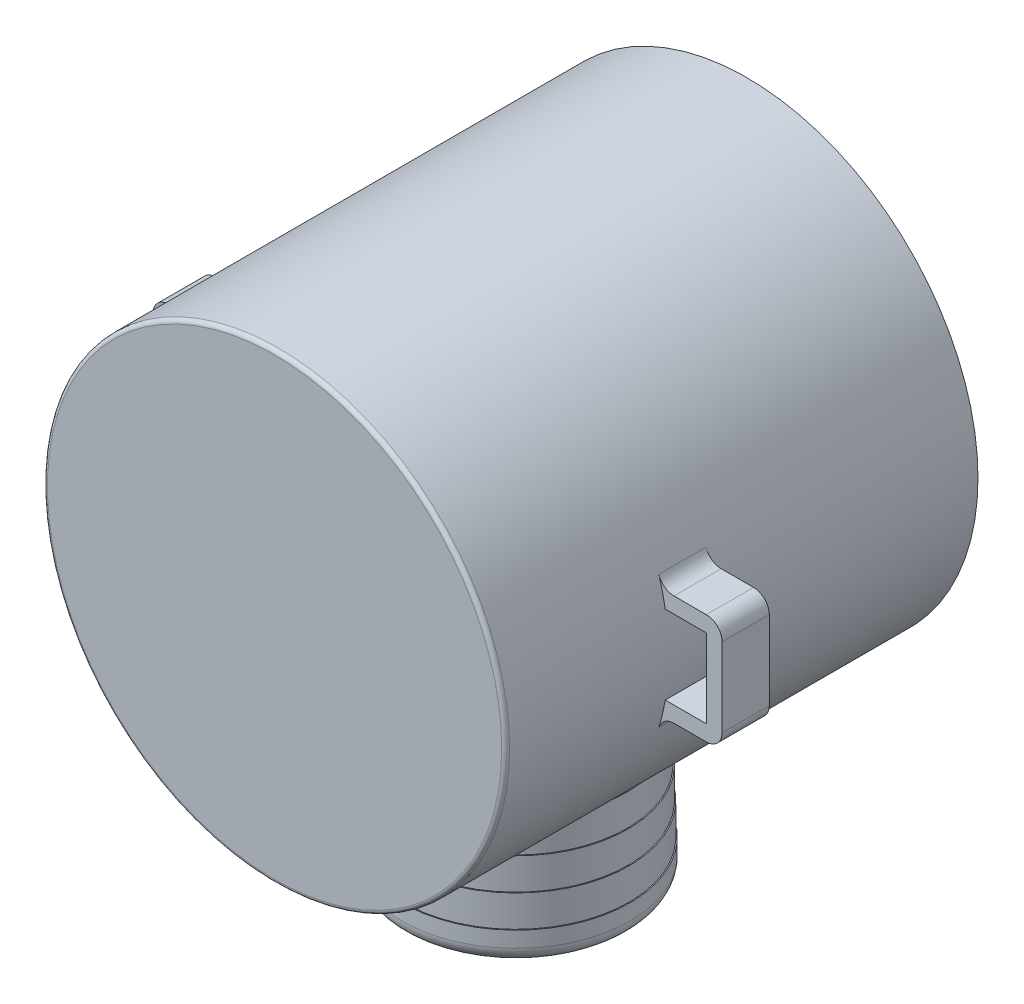
SolidWorks part; units mm, degrees
note: The reader was unsure of these and kept them because the rebuilt part matched: shared geometry of "Sketch3<3>".
ref_plane "Front Plane" through (0, 0, 0) normal (0, 0, 1) x (1, 0, 0)
ref_plane "Top Plane" through (0, 0, 0) normal (0, 1, 0) x (1, 0, 0)
ref_plane "Right Plane" through (0, 0, 0) normal (1, 0, 0) x (0, 0, -1)
sketch "Sketch1" plane through (0, 0, 0) normal (0, 0, 1) x (1, 0, 0)
  circle A0 centre (0, 0) radius 29.35
  circle A1 centre (0, 0) radius 27.5
  dimension "D1" = 55
  dimension "D2" = 58.7
extrude "Boss-Extrude1" add sketch "Sketch1" along normal blind 60
ref_plane "Plane1" through (0, 0, 33.3) normal (0, 0, 1) x (1, 0, 0)
sketch "Sketch2" plane through (0, 0, 33.3) normal (0, 0, 1) x (1, 0, 0)
  line L0 (-48.0014, 0) -> (58.2597, 0) construction
  line L1 (-28.503, 7) -> (-36.143, 7)
  line L2 (-36.143, 7) -> (-36.143, -7)
  line L3 (-36.143, -7) -> (-28.503, -7)
  line L4 (0, 39.654) -> (0, -46.8411) construction
  line L5 (-28.921, 5) -> (-34.143, 5)
  line L6 (-34.143, 5) -> (-34.143, -5)
  line L7 (-34.143, -5) -> (-28.921, -5)
  line L8 (-34.143, -5) -> (-28.503, -5) construction
  line L9 (-28.503, 5) -> (-34.143, 5) construction
  line L10 (28.503, 7) -> (36.143, 7)
  line L11 (36.143, 7) -> (36.143, -7)
  line L12 (36.143, -7) -> (28.503, -7)
  line L13 (34.143, -5) -> (28.921, -5)
  line L14 (34.143, 5) -> (34.143, -5)
  line L15 (28.921, 5) -> (34.143, 5)
  circle A0 centre (0, 0) radius 29.35 construction
  arc A2 (-28.503, 7) -> (-28.921, 5) centre (0, 0) ccw
  arc A3 (-28.921, -5) -> (-28.503, -7) centre (0, 0) ccw
  arc A4 (28.921, -5) -> (28.503, -7) centre (0, 0) cw
  arc A5 (28.503, 7) -> (28.921, 5) centre (0, 0) cw
  point P11 (-36.143, 0)
  dimension "D1" = 14
  dimension "D2" = 7.64
  dimension "D3" = 2
extrude "Boss-Extrude2" add sketch "Sketch2" along normal blind 6
fillet "Fillet1" radius 2 8 edges at (36.143, 7, 36.3) (36.143, -7, 36.3) (-36.143, 7, 36.3) (-36.143, -7, 36.3) (-28.503, -7, 36.3) (-28.503, 7, 36.3) (28.503, -7, 36.3) (28.503, 7, 36.3)
fillet "Fillet2" radius 0.5 1 edges at (29.35, 0, 60)
ref_plane "Plane3" through (0, -29.35, 0) normal (0, -1, 0) x (-1, 0, 0)
sketch "Sketch3" plane through (0, -29.35, 0) normal (0, -1, 0) x (-1, 0, 0)
  line L0 (29.35, -59.5) -> (29.35, 0) construction
  line L1 (-29.35, 0) -> (-29.35, -59.5) construction
  line L2 (-29.35, -59.5) -> (29.35, -59.5) construction
  line L3 (29.35, 0) -> (-29.35, 0) construction
  line L4 (29.35, -59.5) -> (29.35, 0) construction
  line L5 (-29.35, 0) -> (-29.35, -59.5) construction
  line L6 (-29.35, -59.5) -> (29.35, -59.5) construction
  line L7 (29.35, 0) -> (-29.35, 0) construction
  line L8 (12.85, 0) -> (12.85, -59.5) construction
  line L9 (-29.35, -16.5) -> (29.35, -16.5) construction
  circle A0 centre (12.85, -16.5) radius 14
  circle A1 centre (12.85, -16.5) radius 11.5
  dimension "D3" = 28
  dimension "D4" = 2.5
  dimension "D1" = 16.5
  dimension "D2" = 43
extrude "Boss-Extrude3" add sketch "Sketch3" against normal up to surface (2.9625 mm away)
extrude "Boss-Extrude4" add sketch "Sketch3<3>" along normal blind 11
sketch "Sketch3<3>" plane through (0, -29.35, 0) normal (0, -1, 0) x (-1, 0, 0) same geometry as "Sketch3"
sketch "Sketch4" plane through (0, -40.35, 0) normal (0, -1, 0) x (-1, 0, 0)
  circle A0 centre (12.85, -16.5) radius 11.5
  circle A1 centre (12.85, -16.5) radius 14.125
  dimension "D1" = 28.25
extrude "Boss-Extrude5" add sketch "Sketch4" along normal blind 4
sketch "Sketch5" plane through (0, -44.35, 0) normal (0, -1, 0) x (1, 0, 0)
  circle A0 centre (-12.85, 16.5) radius 11.5
  circle A1 centre (-12.85, 16.5) radius 14.25
  dimension "D1" = 28.5
extrude "Boss-Extrude6" add sketch "Sketch5" along normal blind 4
sketch "Sketch6" plane through (0, -48.35, 0) normal (0, -1, 0) x (1, 0, 0)
  circle A0 centre (-12.85, 16.5) radius 11.5
  circle A1 centre (-12.85, 16.5) radius 14.375
  dimension "D1" = 28.75
extrude "Boss-Extrude7" add sketch "Sketch6" along normal blind 4
sketch "Sketch7" plane through (0, -52.35, 0) normal (0, -1, 0) x (-1, 0, 0)
  circle A0 centre (12.85, -16.5) radius 11.5
  circle A1 centre (12.85, -16.5) radius 14.5
  dimension "D1" = 29
extrude "Boss-Extrude8" add sketch "Sketch7" along normal blind 4
fillet "Fillet3" radius 2 1 edges at (-12.85, -56.35, 2)
sketch "Sketch8" plane through (0, -56.35, 0) normal (0, -1, 0) x (1, 0, 0)
  circle A0 centre (-12.85, 16.5) radius 11.5
extrude "Cut-Extrude1" cut sketch "Sketch8" against normal up to next
sketch "Sketch9" plane through (0, 0, 60) normal (0, 0, 1) x (1, 0, 0)
  circle A0 centre (0, 0) radius 27.5
extrude "Boss-Extrude9" add sketch "Sketch9" against normal blind 0.5
